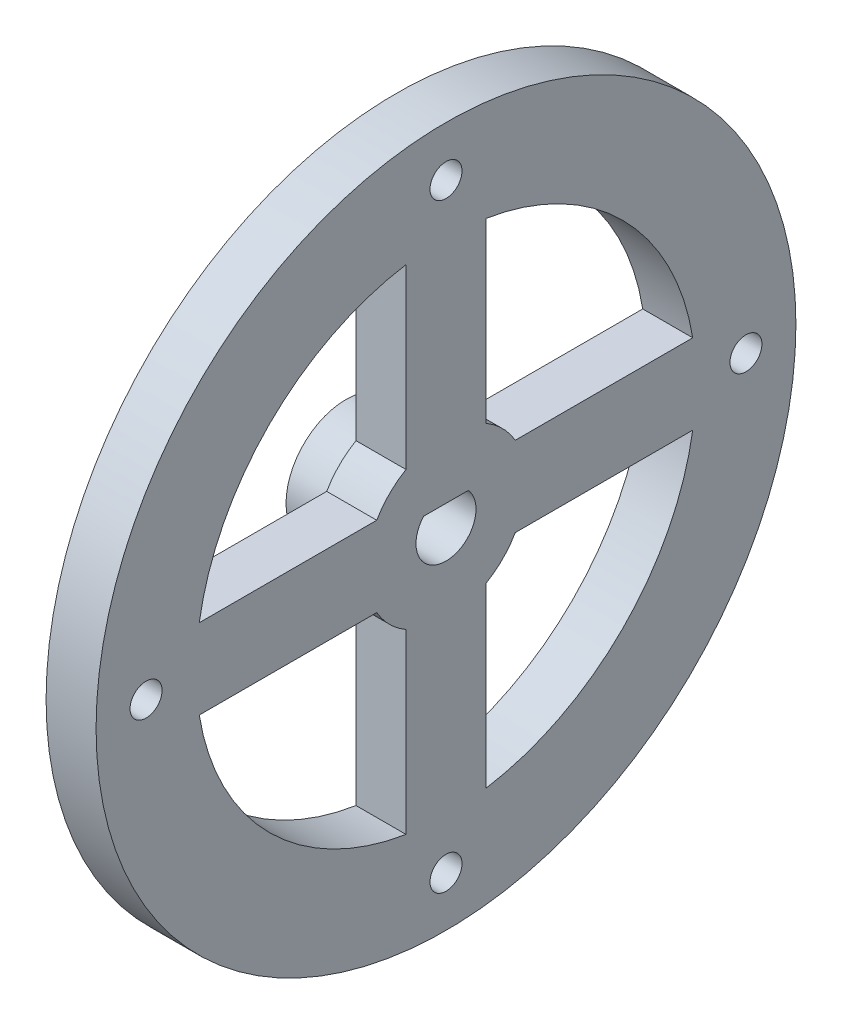
SolidWorks part; units mm, degrees
ref_plane "Front Plane" through (0, 0, 0) normal (0, 0, 1) x (1, 0, 0)
ref_plane "Top Plane" through (0, 0, 0) normal (0, 1, 0) x (1, 0, 0)
ref_plane "Right Plane" through (0, 0, 0) normal (1, 0, 0) x (0, 0, -1)
sketch "Sketch1" plane through (0, 0, 0) normal (1, 0, 0) x (0, 0, -1)
  line L0 (0, 0) -> (0, 50000) construction
  line L1 (4, 6.9282) -> (4, 24.6779)
  line L2 (-4, 24.6779) -> (-4, 6.9282)
  line L3 (-24.6779, -4) -> (-6.9282, -4)
  line L4 (-6.9282, 4) -> (-24.6779, 4)
  line L5 (4, -24.6779) -> (4, -6.9282)
  line L6 (-4, -6.9282) -> (-4, -24.6779)
  line L7 (24.6779, 4) -> (6.9282, 4)
  line L8 (6.9282, -4) -> (24.6779, -4)
  line L9 (2.2361, 2) -> (-2.2361, 2)
  circle A0 centre (0, 0) radius 35
  arc A1 (-2.2361, 2) -> (2.2361, 2) centre (0, 0) ccw
  arc A2 (-6.9282, -4) -> (-4, -6.9282) centre (0, 0) ccw
  arc A3 (-24.6779, -4) -> (-4, -24.6779) centre (0, 0) ccw
  arc A4 (-4, 6.9282) -> (-6.9282, 4) centre (0, 0) ccw
  arc A5 (24.6779, 4) -> (4, 24.6779) centre (0, 0) ccw
  arc A6 (4, -24.6779) -> (24.6779, -4) centre (0, 0) ccw
  arc A7 (4, -6.9282) -> (6.9282, -4) centre (0, 0) ccw
  arc A8 (6.9282, 4) -> (4, 6.9282) centre (0, 0) ccw
  arc A9 (-24.6779, 4) -> (-4, 24.6779) centre (0, 0) cw
  point P27 (0, 0)
  dimension "D1" = 70
  dimension "D2" = 6
  dimension "D5" = 16
  dimension "D6" = 50
  dimension "D3" = 8
  dimension "D7" = 2
  dimension "D4" = 4
extrude "Boss-Extrude1" add sketch "Sketch1" along normal blind 5
sketch "Sketch2" plane through (0, 0, 0) normal (-1, 0, 0) x (0, 0, 1)
  circle A0 centre (0, 0) radius 30 construction
  circle A1 centre (0, 30) radius 1.6
  circle A2 centre (30, 0) radius 1.6
  circle A3 centre (0, -30) radius 1.6
  circle A4 centre (-30, 0) radius 1.6
  point P14 (0, 0)
  dimension "D1" = 60
  dimension "D2" = 3.2
  dimension "D3" = 4
extrude "Cut-Extrude1" cut sketch "Sketch2" against normal through all
sketch "Sketch3" plane through (0, 0, 0) normal (-1, 0, 0) x (0, 0, 1)
  line L0 (-2.2361, 2) -> (2.2361, 2) construction
  line L1 (-2.2361, 2) -> (2.2361, 2)
  circle A2 centre (0, 0) radius 6
  arc A3 (-2.2361, 2) -> (2.2361, 2) centre (0, 0) ccw construction
  arc A4 (-2.2361, 2) -> (2.2361, 2) centre (0, 0) ccw
  dimension "D1" = 12
extrude "Boss-Extrude2" add sketch "Sketch3" along normal blind 5
sketch "Sketch6" plane through (0, 0, 0) normal (-1, 0, 0) x (0, 0, 1)
  circle A0 centre (0, 30) radius 4
  circle A1 centre (30, 0) radius 4
  circle A2 centre (0, -30) radius 4
  circle A3 centre (-30, 0) radius 4
  point P12 (0, 0)
  dimension "D1" = 8
  dimension "D2" = 4
extrude "Cut-Extrude2" cut sketch "Sketch6" against normal blind 2
sketch "Sketch7" plane through (-5, 0, 0) normal (-1, 0, 0) x (0, 0, 1)
  line L0 (-3.9116, -3.3007) -> (-3.9116, 3.3007)
  line L1 (3.9116, 3.3007) -> (3.9116, -3.3007)
  arc A2 (-3.9116, -3.3007) -> (3.9116, -3.3007) centre (0, 0) ccw
  arc A3 (3.9116, 3.3007) -> (-3.9116, 3.3007) centre (0, 0) ccw
  dimension "D2" = 10.2362
  dimension "D1" = 7.8232
extrude "Cut-Extrude3" cut sketch "Sketch7" against normal blind 2.3876 contours A3 L0 A2 L1
